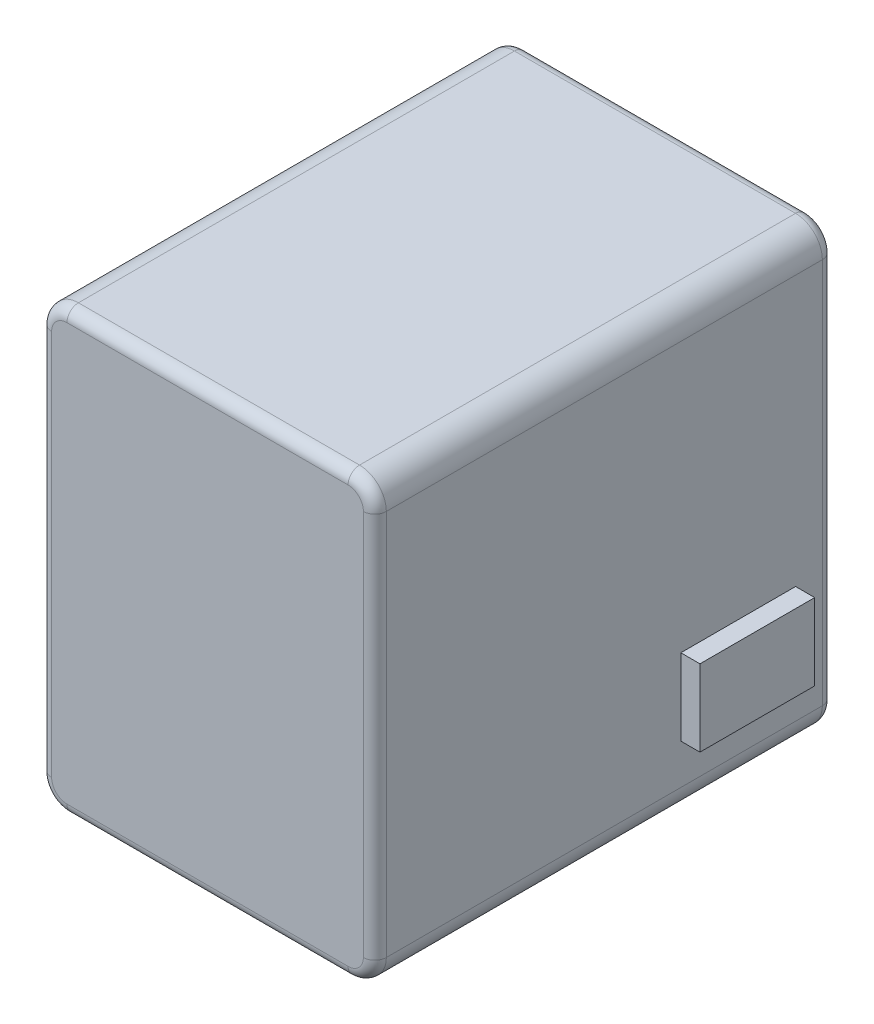
SolidWorks part; units mm, degrees
material "PE High Density"
ref_plane "Front Plane" through (0, 0, 0) normal (0, 0, 1) x (1, 0, 0)
ref_plane "Top Plane" through (0, 0, 0) normal (0, 1, 0) x (1, 0, 0)
ref_plane "Right Plane" through (0, 0, 0) normal (1, 0, 0) x (0, 0, -1)
sketch "Block sketch 1" plane through (0, 0, 0) normal (0, 0, 1) x (1, 0, 0)
  line L0 (684, -115) -> (831, -115)
  line L1 (845, -101) -> (845, 101)
  line L2 (831, 115) -> (684, 115)
  line L3 (670, 101) -> (670, -101)
  arc A0 (831, -115) -> (845, -101) centre (831, -101) ccw
  arc A1 (845, 101) -> (831, 115) centre (831, 101) ccw
  arc A2 (684, 115) -> (670, 101) centre (684, 101) ccw
  arc A3 (670, -101) -> (684, -115) centre (684, -101) ccw
  dimension "D1" = 14
  dimension "D2" = 175
  dimension "D3" = 230
extrude "Block 1" add sketch "Block sketch 1" along normal blind 240 from offset 303 separate body
fillet "Block edge fillet 1" radius 6 16 edges at (674.1005, -110.8995, 543) (674.1005, 110.8995, 543) (840.8995, 110.8995, 543) (840.8995, -110.8995, 543) (840.8995, 110.8995, 303) (840.8995, -110.8995, 303) (757.5, -115, 303) (674.1005, -110.8995, 303) (670, 0, 303) (674.1005, 110.8995, 303) (845, 0, 543) (670, 0, 543) (757.5, 115, 543) (757.5, -115, 543) (845, 0, 303) (757.5, 115, 303)
sketch "Extrude sketch 1" plane through (0, 0, 0) normal (0, 0, 1) x (1, 0, 0)
  line L0 (-30, -20) -> (30, -20)
  line L1 (30, -20) -> (30, 20)
  line L2 (30, 20) -> (-30, 20)
  line L3 (-30, 20) -> (-30, -20)
  dimension "D1" = 60
  dimension "D2" = 40
extrude "Extrude 1" add sketch "Extrude sketch 1" along normal blind 10 separate body
move or copy body "Extrude rotate 1" bodies to move or copy 102 copy no rotation origin (0, 0, 0) rotation axis (0, 1, 0) rotation angle 90
move or copy body "Extrude place 1" bodies to move or copy 103 copy no translate (845, -60, 353) parameters "D1"=845, "D2"=60, "D3"=353
combine bodies "Combine (weld / assembly of features)" operation type add bodies to combine 104 101
